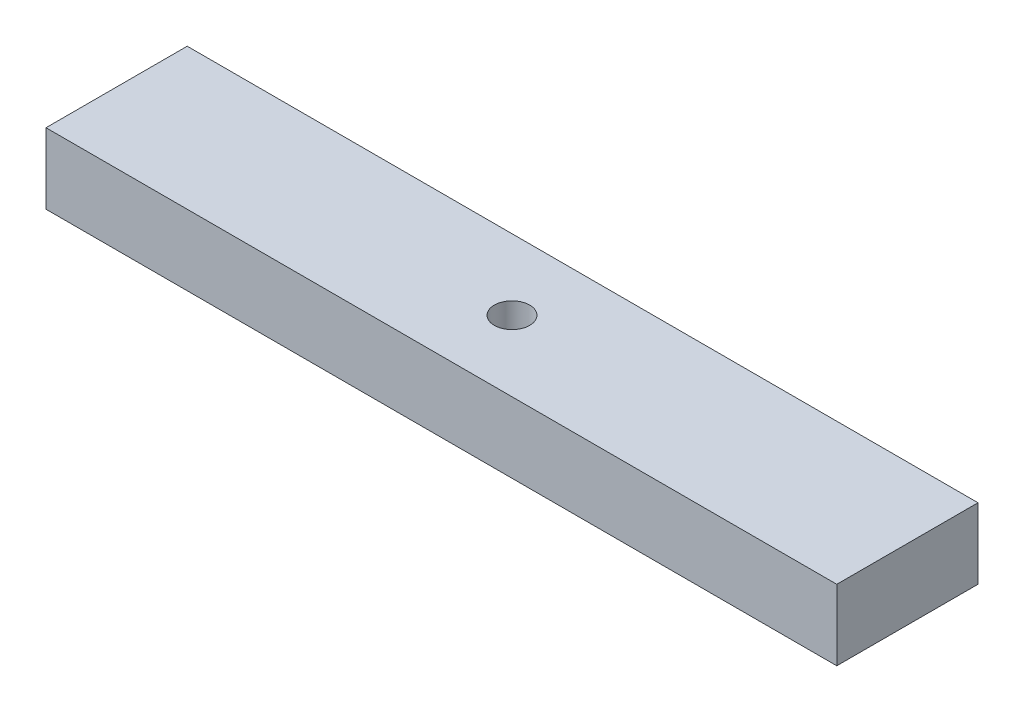
SolidWorks part; units mm, degrees
ref_plane "Front Plane" through (0, 0, 0) normal (0, 0, 1) x (1, 0, 0)
ref_plane "Top Plane" through (0, 0, 0) normal (0, 1, 0) x (1, 0, 0)
ref_plane "Right Plane" through (0, 0, 0) normal (1, 0, 0) x (0, 0, -1)
sketch "Sketch1" plane through (0, 0, 0) normal (0, 1, 0) x (1, 0, 0)
  line L1 (0, 0) -> (142.24, 0)
  line L2 (0, 0) -> (0, 25.4)
  line L3 (0, 25.4) -> (142.24, 25.4)
  line L4 (142.24, 0) -> (142.24, 25.4)
  circle A0 centre (71.12, 12.7) radius 3.175
  point P9 (0, 10.3881)
  dimension "D3" = 6.35
  dimension "D4" = 12.7
  dimension "D1" = 142.24
  dimension "D2" = 25.4
  dimension "D5" = 71.12
extrude "Boss-Extrude1" add sketch "Sketch1" along normal blind 12.7
